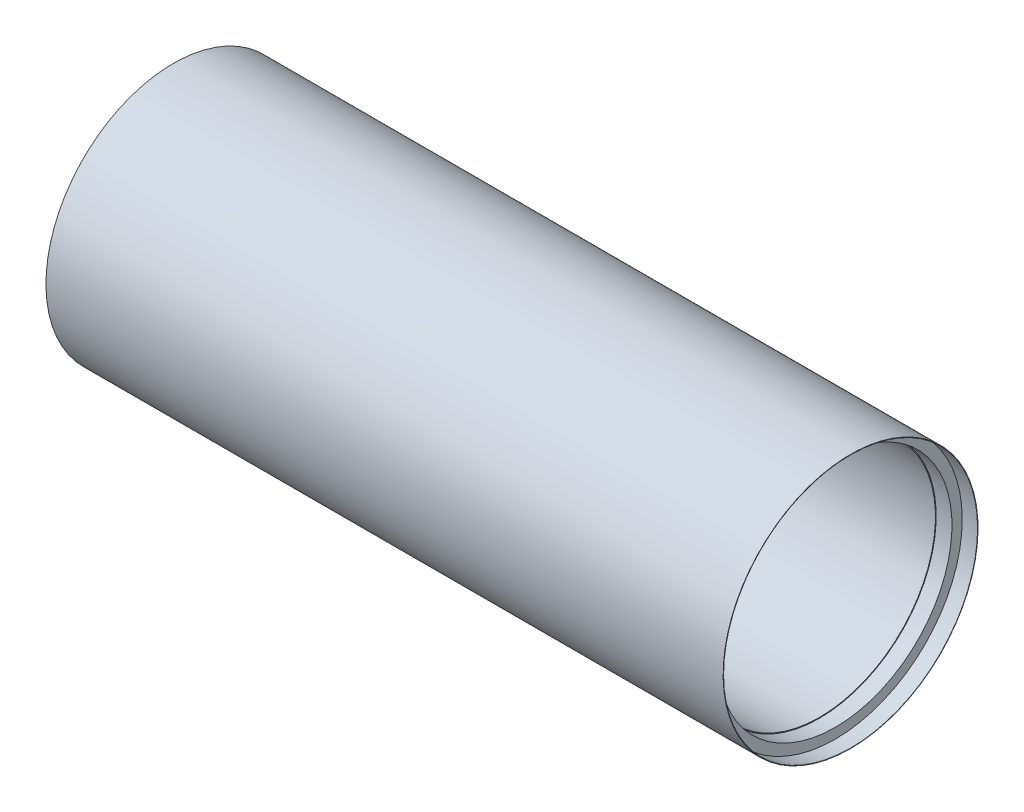
SolidWorks part; units mm, degrees
material "Hexcel AS4C (3000 Filaments)"
ref_plane "Front" through (0, 0, 0) normal (0, 0, 1) x (1, 0, 0)
ref_plane "Top" through (0, 0, 0) normal (0, 1, 0) x (1, 0, 0)
ref_plane "Right" through (0, 0, 0) normal (1, 0, 0) x (0, 0, -1)
sketch "Sketch1" plane through (0, 0, 0) normal (0, 0, 1) x (1, 0, 0)
  line L0 (0, 83.9724) -> (10.16, 83.9724)
  line L1 (10.16, 83.9724) -> (10.16, 77.2414)
  line L2 (20.574, 76.7334) -> (427.5582, 76.7334)
  line L3 (437.9722, 77.2414) -> (437.9722, 84.0486)
  line L4 (437.9722, 84.0486) -> (448.1322, 84.0486)
  line L5 (448.1322, 84.0486) -> (448.1322, 84.3534)
  line L6 (448.1322, 84.3534) -> (0, 84.3534)
  line L7 (0, 84.3534) -> (0, 83.9724)
  line L8 (0, 0) -> (134.0356, 0) construction
  line L9 (10.16, 77.2414) -> (20.574, 77.2414)
  line L10 (20.574, 77.2414) -> (20.574, 76.7334)
  line L11 (437.9722, 77.2414) -> (427.5582, 77.2414)
  line L12 (427.5582, 77.2414) -> (427.5582, 76.7334)
  line L13 (0, 0) -> (0, 83.9724) construction
  dimension "D1" = 76.7334
  dimension "D2" = 0.381
  dimension "D3" = 10.16
  dimension "D4" = 10.16
  dimension "D5" = 427.8122
  dimension "D6" = 84.3534
  dimension "D7" = 0.3048
  dimension "D8" = 10.414
  dimension "D9" = 10.414
  dimension "D10" = 0.508
  dimension "D11" = 0.508
revolve "Revolve1" add sketch "Sketch1" angle 360 about L8 region at (224.014, 80.5627, 0)
